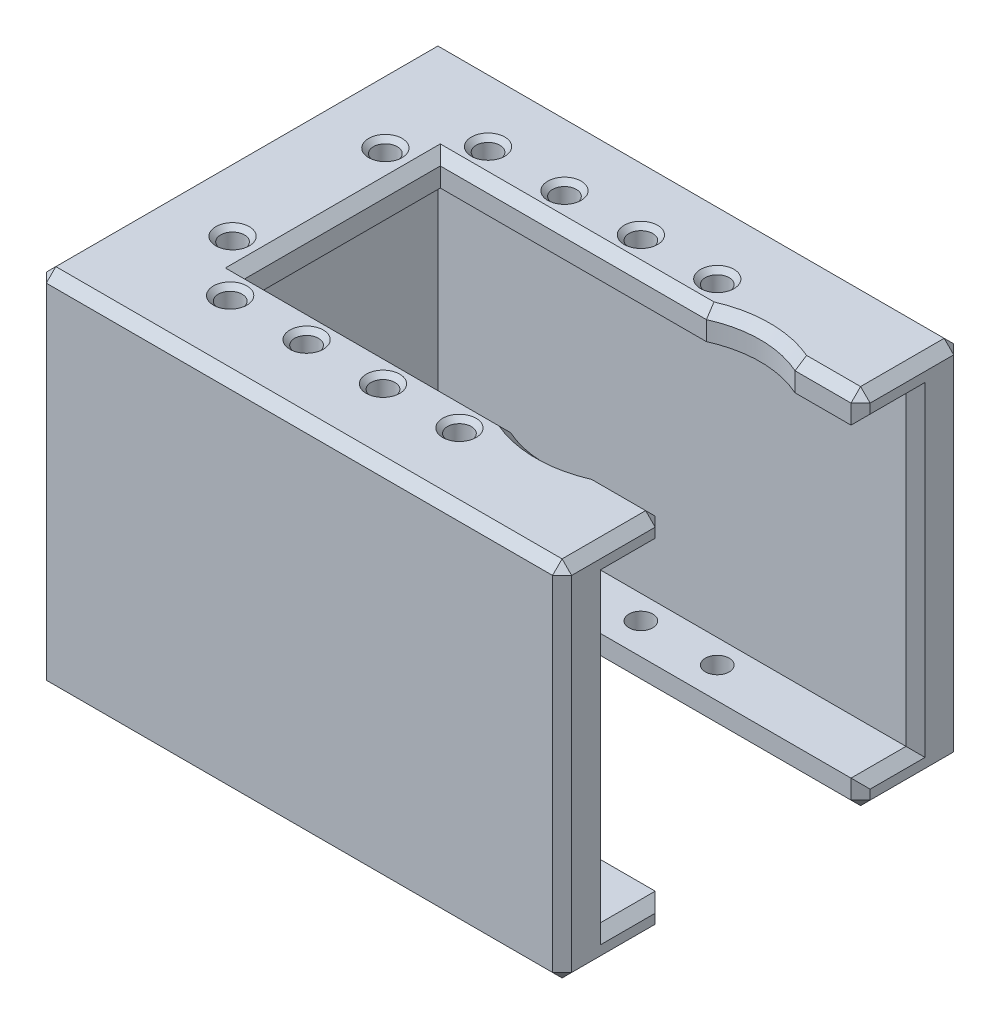
SolidWorks part; units mm, degrees
ref_plane "Front Plane" through (0, 0, 0) normal (0, 0, 1) x (1, 0, 0)
ref_plane "Top Plane" through (0, 0, 0) normal (0, 1, 0) x (1, 0, 0)
ref_plane "Right Plane" through (0, 0, 0) normal (1, 0, 0) x (0, 0, -1)
sketch "Sketch1" plane through (0, 0, 0) normal (0, 0, 1) x (1, 0, 0)
  line L1 (-25, -19) -> (25, -19)
  line L2 (-25, -19) -> (-25, 19)
  line L3 (-25, 19) -> (25, 19)
  line L4 (25, -19) -> (25, 19)
  line L5 (-25, -19) -> (25, 19) construction
  line L6 (-25, 19) -> (25, -19) construction
  point P0 (0, 0)
  dimension "D1" = 38
  dimension "D2" = 50
extrude "Boss-Extrude1" add sketch "Sketch1" along normal blind 5
sketch "Sketch2" plane through (0, 19, 0) normal (0, 1, 0) x (1, 0, 0)
  line L0 (25, -5) -> (-25, -5) construction
  line L1 (-25, -5) -> (25, -5)
  line L2 (-25, -5) -> (-25, -36.9984)
  line L3 (-25, -36.9984) -> (25, -36.9984)
  line L4 (25, -5) -> (25, -10.75)
  line L6 (25, -10.75) -> (18.1368, -10.75)
  line L8 (25, -31.25) -> (18.1368, -31.25)
  line L9 (-19, -10.75) -> (-19, -31.25)
  line L10 (25, -10.75) -> (-19, -31.25) construction
  line L11 (25, -31.25) -> (-19, -10.75) construction
  line L12 (25, -31.25) -> (25, -36.9984)
  line L13 (8.8632, -31.25) -> (-19, -31.25)
  line L14 (8.8632, -10.75) -> (-19, -10.75)
  arc A0 (8.8632, -31.25) -> (18.1368, -31.25) centre (13.5, -21) ccw
  arc A1 (18.1368, -10.75) -> (8.8632, -10.75) centre (13.5, -21) ccw
  point P7 (3, -21)
  dimension "D6" = 22.5
  dimension "D1" = 31.9984
  dimension "D2" = 50
  dimension "D3" = 20.5
  dimension "D4" = 5.75
  dimension "D5" = 6
extrude "Boss-Extrude2" add sketch "Sketch2" against normal blind 3
sketch "Sketch3" plane through (-25, 0, 0) normal (-1, 0, 0) x (0, 0, 1)
  line L0 (5, -19) -> (0, -19) construction
  line L1 (0, 19) -> (36.9984, 19)
  line L2 (0, 19) -> (0, -19)
  line L3 (0, -19) -> (36.9984, -19)
  line L4 (36.9984, 19) -> (36.9984, -19)
  line L5 (36.9984, 16) -> (36.9984, 19) construction
extrude "Boss-Extrude3" add sketch "Sketch3" along normal blind 5
sketch "Sketch4" plane through (0, 0, 36.9984) normal (0, 0, 1) x (1, 0, 0)
  line L1 (-30, 19) -> (25, 19)
  line L2 (-30, 19) -> (-30, -19)
  line L3 (-30, -19) -> (25, -19)
  line L4 (25, 19) -> (25, -19)
extrude "Boss-Extrude4" add sketch "Sketch4" along normal blind 5
sketch "Sketch7" plane through (0, -19, 0) normal (0, -1, 0) x (1, 0, 0)
  line L0 (25, 10.75) -> (25, 5)
  line L1 (-25, 36.9984) -> (25, 36.9984)
  line L2 (-25, 36.9984) -> (-25, 5)
  line L3 (-25, 5) -> (25, 5)
  line L4 (25, 36.9984) -> (25, 31.25)
  line L5 (25, 10.75) -> (-19, 10.75)
  line L7 (25, 31.25) -> (-19, 31.25)
  line L8 (-19, 10.75) -> (-19, 31.25)
extrude "Boss-Extrude7" add sketch "Sketch7" against normal blind 3
sketch "Sketch8" plane through (0, 19, 0) normal (0, 1, 0) x (1, 0, 0)
  line L0 (-30, -20.9992) -> (29.2842, -20.9992) construction
  line L3 (-30, -7.5) -> (25, -7.5) construction
  line L4 (25, -10.75) -> (25, -5) construction
  line L6 (-19, -10.75) -> (8.8632, -10.75) construction
  line L7 (-25, -5) -> (-25, -36.9984) construction
  line L8 (-30, -41.9984) -> (-30, 0) construction
  circle A5 centre (-22.5, -13) radius 1.25
  circle A6 centre (-17.25, -7.5) radius 1.25
  circle A7 centre (-9.25, -7.5) radius 1.25
  circle A8 centre (-1.25, -7.5) radius 1.25
  circle A9 centre (6.75, -7.5) radius 1.25
  circle A10 centre (6.75, -34.4984) radius 1.25
  circle A11 centre (-1.25, -34.4984) radius 1.25
  circle A12 centre (-9.25, -34.4984) radius 1.25
  circle A13 centre (-17.25, -34.4984) radius 1.25
  circle A14 centre (-22.5, -28.9984) radius 1.25
  dimension "D3" = 8
  dimension "D4" = 8
  dimension "D5" = 8
  dimension "D7" = 2.5
  dimension "D1" = 3.25
  dimension "D2" = 7.75
  dimension "D6" = 5.5
extrude "Cut-Extrude1" cut sketch "Sketch8" against normal through all
chamfer "Chamfer3" distance 0.5 angle 45 20 edges at (6.75, -19, 33.2484) (-1.25, -19, 33.2484) (-9.25, -19, 33.2484) (-17.25, -19, 33.2484) (-22.5, -19, 27.7484) (-22.5, -19, 14.25) (-17.25, -19, 8.75) (-9.25, -19, 8.75) (-1.25, -19, 8.75) (6.75, -19, 8.75) (6.75, 19, 8.75) (-1.25, 19, 8.75) (-9.25, 19, 8.75) (-17.25, 19, 8.75) (-22.5, 19, 14.25) (-22.5, 19, 27.7484) (-17.25, 19, 33.2484) (-9.25, 19, 33.2484) (-1.25, 19, 33.2484) (6.75, 19, 33.2484)
chamfer "Chamfer4" distance 1 angle 45 34 edges at (25, 17.5, 31.25) (25, 16, 34.1242) (25, 0, 36.9984) (25, -16, 34.1242) (25, -17.5, 31.25) (25, -19, 36.6242) (25, 19, 36.6242) (25, -19, 5.375) (-2.5, 19, 0) (-30, 19, 20.9992) (-2.5, 19, 41.9984) (25, 0, 41.9984) (-2.5, -19, 41.9984) (-30, 0, 41.9984) (-30, -19, 20.9992) (-30, 0, 0) (-2.5, -19, 0) (25, 0, 0) (25, 19, 5.375) (21.5684, 19, 31.25) (13.5, 19, 32.25) (-5.0684, 19, 31.25) (-19, 19, 21) (-5.0684, 19, 10.75) (13.5, 19, 9.75) (21.5684, 19, 10.75) (25, 17.5, 10.75) (25, 16, 7.875) (25, 0, 5) (25, -16, 7.875) (25, -17.5, 10.75) (3, -19, 10.75) (-19, -19, 21) (3, -19, 31.25)
